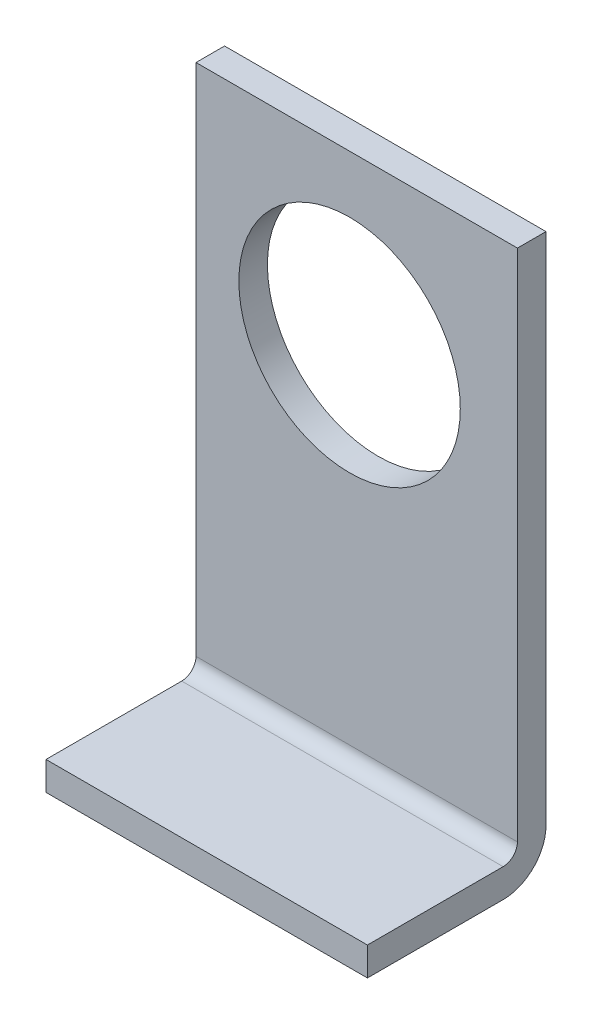
SolidWorks part; units mm, degrees
ref_plane "Front Plane" through (0, 0, 0) normal (0, 0, 1) x (1, 0, 0)
ref_plane "Top Plane" through (0, 0, 0) normal (0, 1, 0) x (1, 0, 0)
ref_plane "Right Plane" through (0, 0, 0) normal (1, 0, 0) x (0, 0, -1)
sketch "Sketch1" plane through (0, 0, 0) normal (0, 1, 0) x (1, 0, 0)
  line L1 (0, 0) -> (22.5, 0)
  line L2 (0, 0) -> (0, 12.5)
  line L3 (0, 12.5) -> (22.5, 12.5)
  line L4 (22.5, 0) -> (22.5, 12.5)
  dimension "D1" = 12.5
  dimension "D2" = 22.5
extrude "Boss-Extrude1" add sketch "Sketch1" along normal blind 2
sketch "Sketch2" plane through (0, 0, -12.5) normal (0, 0, -1) x (-1, 0, 0)
  line L1 (-22.5, 2) -> (0, 2)
  line L2 (-22.5, 2) -> (-22.5, 39)
  line L3 (-22.5, 39) -> (0, 39)
  line L4 (0, 2) -> (0, 39)
  dimension "D1" = 37
extrude "Boss-Extrude2" add sketch "Sketch2" against normal blind 2
fillet "Fillet1" radius 1 1 edges at (11.25, 2, -10.5)
fillet "Fillet2" radius 3 1 edges at (11.25, 0, -12.5)
sketch "Sketch5" plane through (0, 0, -12.5) normal (0, 0, -1) x (-1, 0, 0)
  line L1 (-22.5, 39) -> (-22.5, 3) construction
  line L2 (0, 39) -> (-22.5, 39) construction
  circle A0 centre (-10.75, 27.25) radius 7.75
  dimension "D1" = 4
  dimension "D2" = 4
  dimension "D3" = 15.5
extrude "Cut-Extrude1" cut sketch "Sketch5" against normal blind 2 contours A0
